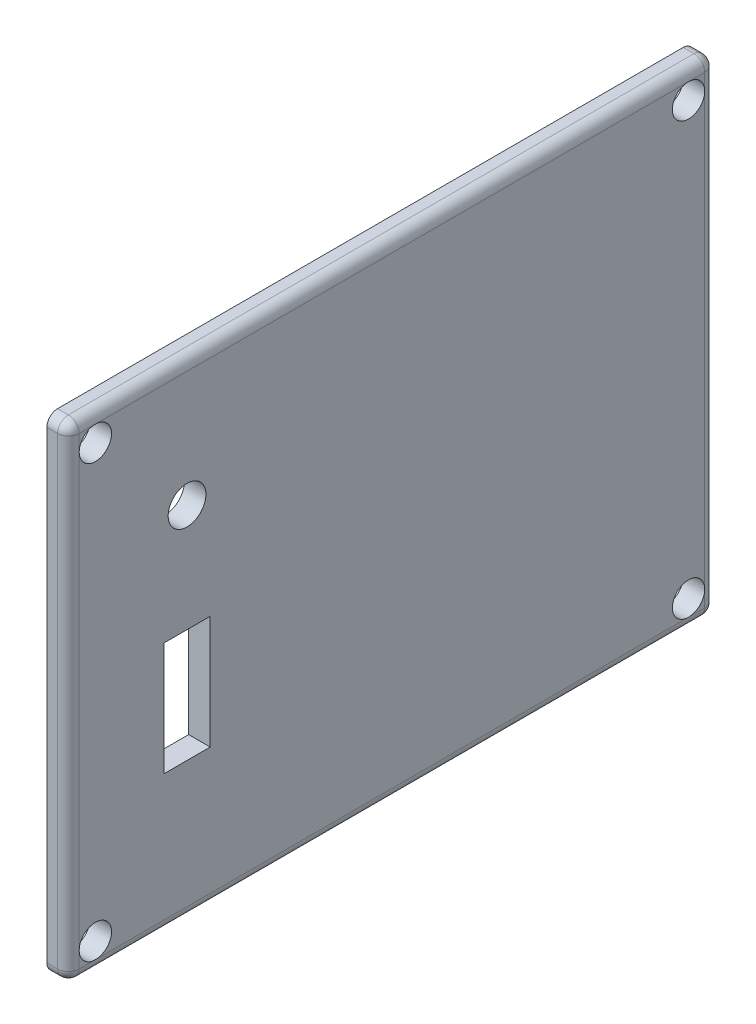
SolidWorks part; units mm, degrees
ref_plane "Front Plane" through (0, 0, 0) normal (0, 0, 1) x (1, 0, 0)
ref_plane "Top Plane" through (0, 0, 0) normal (0, 1, 0) x (1, 0, 0)
ref_plane "Right Plane" through (0, 0, 0) normal (1, 0, 0) x (0, 0, -1)
sketch "Sketch1" plane through (0, 0, 0) normal (1, 0, 0) x (0, 0, -1)
  line L1 (-30, -22.5) -> (30, -22.5)
  line L2 (-30, -22.5) -> (-30, 22.5)
  line L3 (-30, 22.5) -> (30, 22.5)
  line L4 (30, -22.5) -> (30, 22.5)
  line L5 (-30, -22.5) -> (30, 22.5) construction
  line L6 (-30, 22.5) -> (30, -22.5) construction
  point P0 (0, 0)
  dimension "D1" = 60
  dimension "D2" = 45
extrude "Boss-Extrude1" add sketch "Sketch1" along normal blind 2
hole_wizard "Ø3.0mm Dowel Hole1" positions "Sketch2" profile "Sketch3" hole size "Ø3.0" standard "ANSI Metric"
sketch "Sketch2" plane through (2, 0, 0) normal (1, 0, 0) x (0, 0, -1)
  line L0 (30, 22.5) -> (-30, 22.5) construction
  line L1 (-30, 22.5) -> (-30, -22.5) construction
  line L2 (-30, -22.5) -> (30, -22.5) construction
  line L3 (30, -22.5) -> (30, 22.5) construction
  point P0 (-27.5, 20)
  point P2 (27.5, 20)
  point P4 (27.5, -20)
  point P6 (-27.5, -20)
  point P9 (0, 0)
  point P10 (0, 0)
  point P11 (0, 0)
  point P12 (0, 0)
  dimension "D1" = 2.5
  dimension "D2" = 2.5
  dimension "D3" = 2.5
  dimension "D4" = 2.5
sketch "Sketch3" plane through (2, 20, 27.5) normal (0, 1, 0) x (0, 0, -1)
  line L0 (0, 0) -> (0, 20.9013)
  line L1 (0, 20.9013) -> (1.5, 20)
  line L2 (1.5, 20) -> (1.5, 0)
  line L5 (1.5, 0) -> (0, 0)
  line L10 (0, 20.9013) -> (-1.5, 20) construction
  line L11 (0, -6.35) -> (0, 107.95) construction
  dimension "Hole Dia." = 3
  dimension "Hole Depth" = 20
  dimension "Drill Angle" = 118
fillet "Fillet2" radius 1 4 edges at (1, -22.5, -30) (1, -22.5, 30) (1, 22.5, -30) (1, 22.5, 30)
fillet "Fillet1" radius 1 8 edges at (2, 0, -30) (2, -22.5, 0) (2, 22.5, 0) (2, 0, 30) (2, 22.2071, 29.7071) (2, 22.2071, -29.7071) (2, -22.2071, -29.7071) (2, -22.2071, 29.7071)
sketch "Sketch4" plane through (2, 0, 0) normal (1, 0, 0) x (0, 0, -1)
  line L0 (-29, 20) -> (-29, -20) construction
  line L1 (-21.15, 0.75) -> (-16.85, 0.75)
  line L2 (-21.15, 0.75) -> (-21.15, -9.75)
  line L3 (-21.15, -9.75) -> (-16.85, -9.75)
  line L4 (-16.85, 0.75) -> (-16.85, -9.75)
  line L5 (-21.15, 0.75) -> (-16.85, -9.75) construction
  line L6 (-21.15, -9.75) -> (-16.85, 0.75) construction
  line L8 (27.5, 21.5) -> (-27.5, 21.5) construction
  circle A0 centre (-19, 10.75) radius 1.75
  point P0 (-19, -4.5)
  point P7 (-19, 0.75)
  point P13 (-19, 13)
  point P14 (-19, 13)
  point P15 (0, 0)
  point P16 (0, 0)
  point P17 (0, 0)
  point P18 (-19, -4.3764)
  dimension "D4" = 3.5
  dimension "D1" = 4.3
  dimension "D2" = 10.5
  dimension "D3" = 10
  dimension "D5" = 10
  dimension "D6" = 26
extrude "Cut-Extrude1" cut sketch "Sketch4" against normal blind 3
equation "\"D2@Sketch2\"=\"D1@Sketch2\""
equation "\"D3@Sketch2\"=\"D1@Sketch2\""
equation "\"D4@Sketch2\"=\"D1@Sketch2\""
